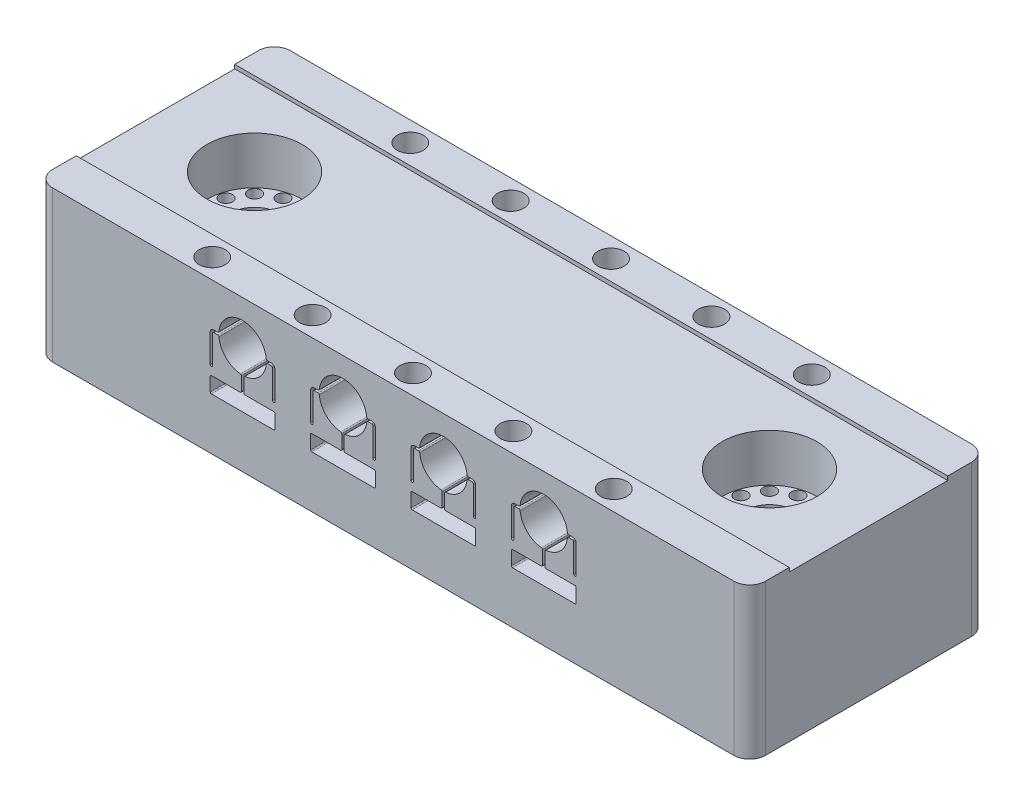
SolidWorks part; units mm, degrees
ref_plane "Front Plane" through (0, 0, 0) normal (0, 0, 1) x (1, 0, 0)
ref_plane "Top Plane" through (0, 0, 0) normal (0, 1, 0) x (1, 0, 0)
ref_plane "Right Plane" through (0, 0, 0) normal (1, 0, 0) x (0, 0, -1)
sketch "Sketch1" plane through (0, 0, 0) normal (0, 1, 0) x (1, 0, 0)
  line L0 (-45, 13) -> (-45, -13)
  line L3 (-43, -15) -> (43, -15)
  line L4 (45, -13) -> (45, 13)
  line L5 (43, 15) -> (-43, 15)
  line L6 (-32.5, 0) -> (32.5, 0) construction
  line L8 (-33.8159, 4.9109) -> (-36.095, 3.595) construction
  line L9 (-36.095, 3.595) -> (-37.4109, 1.3159) construction
  line L10 (-37.4109, 1.3159) -> (-37.4109, -1.3159) construction
  line L11 (-37.4109, -1.3159) -> (-36.095, -3.595) construction
  line L12 (-36.095, -3.595) -> (-33.8159, -4.9109) construction
  line L13 (-33.8159, -4.9109) -> (-31.1841, -4.9109) construction
  line L14 (-31.1841, -4.9109) -> (-28.905, -3.595) construction
  line L15 (-28.905, -3.595) -> (-27.5891, -1.3159) construction
  line L16 (-27.5891, -1.3159) -> (-27.5891, 1.3159) construction
  line L17 (-27.5891, 1.3159) -> (-28.905, 3.595) construction
  line L18 (-28.905, 3.595) -> (-31.1841, 4.9109) construction
  line L19 (-31.1841, 4.9109) -> (-33.8159, 4.9109) construction
  line L20 (33.8159, 4.9109) -> (31.1841, 4.9109) construction
  line L21 (31.1841, 4.9109) -> (28.905, 3.595) construction
  line L22 (28.905, 3.595) -> (27.5891, 1.3159) construction
  line L23 (27.5891, 1.3159) -> (27.5891, -1.3159) construction
  line L24 (27.5891, -1.3159) -> (28.905, -3.595) construction
  line L25 (28.905, -3.595) -> (31.1841, -4.9109) construction
  line L26 (31.1841, -4.9109) -> (33.8159, -4.9109) construction
  line L27 (33.8159, -4.9109) -> (36.095, -3.595) construction
  line L28 (36.095, -3.595) -> (37.4109, -1.3159) construction
  line L29 (37.4109, -1.3159) -> (37.4109, 1.3159) construction
  line L30 (37.4109, 1.3159) -> (36.095, 3.595) construction
  line L31 (36.095, 3.595) -> (33.8159, 4.9109) construction
  circle A2 centre (-32.5, 0) radius 3
  circle A3 centre (32.5, 0) radius 3
  circle A17 centre (32.5, 0) radius 6 construction
  circle A18 centre (-32.5, 0) radius 6 construction
  circle A19 centre (-31.1841, 4.9109) radius 0.9159 construction
  circle A20 centre (-31.1841, 4.9109) radius 0.8159
  circle A21 centre (-32.5, 0) radius 4.9109 construction
  circle A22 centre (-33.8159, 4.9109) radius 0.8159
  circle A23 centre (-33.8159, 4.9109) radius 1.8159 construction
  circle A24 centre (-36.095, 3.595) radius 0.8159
  circle A25 centre (-37.4109, 1.3159) radius 0.8159
  circle A26 centre (-37.4109, -1.3159) radius 0.8159
  circle A27 centre (-36.095, -3.595) radius 0.8159
  circle A28 centre (-33.8159, -4.9109) radius 0.8159
  circle A29 centre (-31.1841, -4.9109) radius 0.8159
  circle A30 centre (-28.905, -3.595) radius 0.8159
  circle A31 centre (-27.5891, -1.3159) radius 0.8159
  circle A32 centre (-27.5891, 1.3159) radius 0.8159
  circle A33 centre (-28.905, 3.595) radius 0.8159
  circle A34 centre (32.5, 0) radius 4.9109 construction
  circle A35 centre (31.1841, 4.9109) radius 0.8159
  circle A36 centre (33.8159, 4.9109) radius 0.8159
  circle A37 centre (36.095, 3.595) radius 0.8159
  circle A38 centre (37.4109, 1.3159) radius 0.8159
  circle A39 centre (37.4109, -1.3159) radius 0.8159
  circle A40 centre (36.095, -3.595) radius 0.8159
  circle A41 centre (33.8159, -4.9109) radius 0.8159
  circle A42 centre (31.1841, -4.9109) radius 0.8159
  circle A43 centre (28.905, -3.595) radius 0.8159
  circle A44 centre (27.5891, -1.3159) radius 0.8159
  circle A45 centre (27.5891, 1.3159) radius 0.8159
  circle A46 centre (28.905, 3.595) radius 0.8159
  arc A47 (43, -15) -> (45, -13) centre (43, -13) ccw
  arc A48 (-45, -13) -> (-43, -15) centre (-43, -13) ccw
  arc A49 (-45, 13) -> (-43, 15) centre (-43, 13) cw
  arc A50 (45, 13) -> (43, 15) centre (43, 13) ccw
  point P2 (-45, 0)
  point P6 (0, 15)
  point P72 (-45, 15)
  point P75 (45, 15)
  dimension "D1" = 90
  dimension "D2" = 12
  dimension "D3" = 65
  dimension "D4" = 6
  dimension "D5" = 30
  dimension "D6" = 0.1
  dimension "D7" = 1.6317
  dimension "D8" = 1
  dimension "D9" = 2
extrude "Boss-Extrude1" add sketch "Sketch1" along normal blind 19.05
sketch "Sketch2" plane through (0, 19.05, 0) normal (0, 1, 0) x (1, 0, 0)
  circle A0 centre (32.5, 0) radius 6 construction
  circle A1 centre (-32.5, 0) radius 6 construction
  circle A2 centre (32.5, 0) radius 6
  circle A3 centre (-32.5, 0) radius 6
extrude "Cut-Extrude1" cut sketch "Sketch2" against normal blind 6.5
sketch "Sketch3" plane through (0, 0, 15) normal (0, 0, 1) x (1, 0, 0)
  line L0 (0, 19.05) -> (0, 13.55) construction
  line L1 (-43, 19.05) -> (43, 19.05) construction
  line L2 (-22.1427, 13.7) -> (-22.6427, 13.7)
  line L3 (-22.1427, 13.4) -> (-22.6427, 13.4)
  line L4 (-23.0927, 13.25) -> (-23.0927, 9.7)
  line L5 (-22.7927, 13.25) -> (-22.7927, 9.7)
  line L6 (-15.8714, 13.7) -> (-15.3714, 13.7)
  line L7 (-15.8714, 13.4) -> (-15.3714, 13.4)
  line L8 (-15.2214, 13.25) -> (-15.2214, 9.7)
  line L9 (-14.9214, 13.25) -> (-14.9214, 9.7)
  line L10 (-19.157, 10.4143) -> (-19.157, 8.7)
  line L11 (-19.307, 8.55) -> (-22.9427, 8.55)
  line L12 (-18.857, 10.4143) -> (-18.857, 8.7)
  line L13 (-18.707, 8.55) -> (-15.0714, 8.55)
  line L14 (-22.9427, 6.5478) -> (-15.0714, 6.5478)
  line L15 (-23.0927, 8.4) -> (-23.0927, 6.6978)
  line L16 (-14.9214, 8.4) -> (-14.9214, 6.6978)
  line L17 (-19.007, 16.55) -> (-19.007, 19.05) construction
  line L18 (-22.1427, 13.4) -> (-22.1427, 13.7) construction
  line L19 (-22.9427, 9.55) -> (-22.9427, 8.55) construction
  line L20 (-19.157, 10.4143) -> (-18.857, 10.4143) construction
  line L21 (-21.507, 6.5478) -> (-21.507, 0) construction
  line L22 (-43, 0) -> (43, 0) construction
  line L23 (-16.507, 6.5478) -> (-16.507, 0) construction
  line L24 (-21.507, 3.2739) -> (-16.507, 3.2739) construction
  line L25 (-19.007, 3.2739) -> (-19.007, 6.5478) construction
  line L26 (-19.007, 8.55) -> (-19.007, 10.55) construction
  line L27 (-21.507, 6.5478) -> (-19.007, 8.05) construction
  line L28 (-19.007, 8.05) -> (-16.507, 6.5478) construction
  line L29 (-19.007, 13.55) -> (-14.9214, 13.55) construction
  line L30 (-14.9214, 13.55) -> (-10.4214, 13.55) construction
  line L31 (-10.4214, 13.55) -> (-6.3357, 13.55) construction
  line L32 (-6.3357, 13.55) -> (-2.25, 13.55) construction
  line L33 (-2.25, 13.55) -> (2.25, 13.55) construction
  line L34 (2.25, 13.55) -> (6.3357, 13.55) construction
  line L35 (6.3357, 13.55) -> (10.4214, 13.55) construction
  line L36 (10.4214, 13.55) -> (14.9214, 13.55) construction
  line L37 (14.9214, 13.55) -> (19.007, 13.55) construction
  arc A0 (-21.9934, 13.2643) -> (-19.2928, 10.5636) centre (-19.007, 13.55) ccw
  arc A1 (-22.6427, 13.7) -> (-23.0927, 13.25) centre (-22.6427, 13.25) ccw
  arc A2 (-22.6427, 13.4) -> (-22.7927, 13.25) centre (-22.6427, 13.25) ccw
  arc A3 (-23.0927, 9.7) -> (-22.7927, 9.7) centre (-22.9427, 9.7) ccw
  arc A4 (-15.3714, 13.7) -> (-14.9214, 13.25) centre (-15.3714, 13.25) cw
  arc A5 (-15.3714, 13.4) -> (-15.2214, 13.25) centre (-15.3714, 13.25) cw
  arc A6 (-15.2214, 9.7) -> (-14.9214, 9.7) centre (-15.0714, 9.7) ccw
  arc A7 (-16.0207, 13.8357) -> (-21.9934, 13.8357) centre (-19.007, 13.55) ccw
  arc A8 (-15.8714, 13.7) -> (-16.0207, 13.8357) centre (-15.8714, 13.85) cw
  arc A9 (-15.8714, 13.4) -> (-16.0207, 13.2643) centre (-15.8714, 13.25) ccw
  arc A10 (-22.1427, 13.4) -> (-21.9934, 13.2643) centre (-22.1427, 13.25) cw
  arc A11 (-22.1427, 13.7) -> (-21.9934, 13.8357) centre (-22.1427, 13.85) ccw
  arc A12 (-18.7213, 10.5636) -> (-16.0207, 13.2643) centre (-19.007, 13.55) ccw
  arc A13 (-19.157, 8.7) -> (-19.307, 8.55) centre (-19.307, 8.7) cw
  arc A14 (-22.9427, 8.55) -> (-23.0927, 8.4) centre (-22.9427, 8.4) ccw
  arc A15 (-23.0927, 6.6978) -> (-22.9427, 6.5478) centre (-22.9427, 6.6978) ccw
  arc A16 (-14.9214, 6.6978) -> (-15.0714, 6.5478) centre (-15.0714, 6.6978) cw
  arc A17 (-15.0714, 8.55) -> (-14.9214, 8.4) centre (-15.0714, 8.4) cw
  arc A18 (-18.857, 8.7) -> (-18.707, 8.55) centre (-18.707, 8.7) ccw
  arc A19 (-18.857, 10.4143) -> (-18.7213, 10.5636) centre (-18.707, 10.4143) cw
  arc A20 (-19.157, 10.4143) -> (-19.2928, 10.5636) centre (-19.307, 10.4143) ccw
  point P30 (-16.0108, 13.7)
  point P59 (-18.857, 10.5538)
  point P87 (-8.3785, 13.55)
  point P88 (0, 0)
  dimension "D1" = 2.5
  dimension "D2" = 1
  dimension "D5" = 3
  dimension "D3" = 0.3
  dimension "D4" = 5
  dimension "D6" = 2
  dimension "D7" = 118
  dimension "D8" = 0.5
  dimension "D9" = 0.5
  dimension "D10" = 4.5
extrude "Cut-Extrude2" cut sketch "Sketch3" against normal through all
pattern_linear "LPattern1" count 4 spacing 12.6714 along (1, 0, 0) of "Cut-Extrude2"
sketch "Sketch4" plane through (0, 19.05, 0) normal (0, 1, 0) x (1, 0, 0)
  line L0 (-45, -10) -> (45, -10)
  line L1 (-45, 13) -> (-45, -13) construction
  line L2 (45, -13) -> (45, 13) construction
  line L3 (45, -10) -> (45, 10)
  line L4 (45, 10) -> (-45, 10)
  line L5 (-45, 10) -> (-45, -10)
  line L6 (10.4214, -15) -> (14.9214, -15) construction
  line L7 (-2.25, -15) -> (2.25, -15) construction
  line L8 (-14.9214, -15) -> (-10.4214, -15) construction
  line L9 (10.4214, -15) -> (14.9214, -15) construction
  line L10 (-2.25, -15) -> (2.25, -15) construction
  line L11 (-14.9214, -15) -> (-10.4214, -15) construction
  line L12 (-14.9214, -15) -> (-23.0927, -15) construction
  line L13 (-43, -15) -> (43, -15) construction
  line L14 (-23.0927, -15) -> (-27.5927, -15) construction
  line L15 (-10.4214, -15) -> (-2.25, -15) construction
  line L16 (-25.3427, -15) -> (-25.3427, -10) construction
  line L17 (-25.3427, 10) -> (-25.3427, 15) construction
  line L18 (43, 15) -> (-43, 15) construction
  line L20 (14.9214, -15) -> (23.0927, -15) construction
  line L21 (23.0927, -15) -> (27.5927, -15) construction
  line L22 (25.3427, -15) -> (25.3427, -10) construction
  circle A0 centre (-25.3427, -12.5) radius 2.5 construction
  circle A1 centre (-25.3427, -12.5) radius 2 construction
  circle A2 centre (-25.3427, 12.5) radius 2.5 construction
  circle A3 centre (-25.3427, 12.5) radius 2 construction
  point P9 (-45, 0)
  point P21 (25.3427, -12.5)
  dimension "D1" = 0.5
  dimension "D2" = 4
sketch "Sketch5" plane through (0, 19.05, 0) normal (0, 1, 0) x (1, 0, 0)
  point P0 (-25.3427, -12.5)
  point P3 (-25.3427, 12.5)
hole_wizard "M4x0.7 Tapped Hole1" positions "Sketch5" profile "Sketch6" tap size "M4x0.7" standard "ANSI Metric"
sketch "Sketch6" plane through (-25.3427, 19.05, 12.5) normal (1, 0, 0) x (0, 0, 1)
  line L0 (0, 0) -> (0, 11.0914)
  line L1 (0, 11.0914) -> (1.65, 10.1)
  line L2 (1.65, 10.1) -> (1.65, 0)
  line L5 (1.65, 0) -> (0, 0)
  line L10 (0, 11.0914) -> (-1.65, 10.1) construction
  line L11 (0, -6.35) -> (0, 107.95) construction
  dimension "Tap Drill Dia." = 3.3
  dimension "Tap Drill Depth" = 10.1
  dimension "Drill Angle" = 118
cosmetic thread "Hole Thread1" parameters "D1"=8, "D2"=4
cosmetic thread "Hole Thread2" parameters "D1"=8, "D2"=4
pattern_linear "LPattern2" count 5 spacing 12.6714 along (1, 0, 0) of "M4x0.7 Tapped Hole1"
cosmetic thread "Hole Thread3" parameters "D1"=8, "D2"=4
cosmetic thread "Hole Thread4" parameters "D1"=8, "D2"=4
cosmetic thread "Hole Thread5" parameters "D1"=8, "D2"=4
cosmetic thread "Hole Thread6" parameters "D1"=8, "D2"=4
cosmetic thread "Hole Thread7" parameters "D1"=8, "D2"=4
cosmetic thread "Hole Thread8" parameters "D1"=8, "D2"=4
cosmetic thread "Hole Thread9" parameters "D1"=8, "D2"=4
cosmetic thread "Hole Thread10" parameters "D1"=8, "D2"=4
extrude "Cut-Extrude3" cut sketch "Sketch4" against normal blind 0.5
sketch "Sketch7" plane through (0, 0, 0) normal (0, -1, 0) x (1, 0, 0)
  line L0 (-22.9427, 15) -> (-15.0714, 15) construction
  line L1 (-22.9427, 15) -> (-15.0714, 15) construction
  line L2 (15.0714, 15) -> (22.9427, 15) construction
  line L3 (15.0714, 15) -> (22.9427, 15) construction
  line L4 (-19.007, 5) -> (-19.007, -5) construction
  circle A0 centre (-19.007, 5) radius 2.5
  circle A1 centre (-19.007, -5) radius 2.5
  point P6 (-19.007, 15)
  point P7 (19.007, 15)
  point P8 (-19.007, 0)
  dimension "D2" = 5
  dimension "D1" = 10
extrude "Cut-Extrude4" cut sketch "Sketch7" against normal up to surface (6.5478 mm away) up to face at (-19.007, 6.5478, 0)
pattern_linear "LPattern3" count 4 spacing 12.6714 along (1, 0, 0) of "Cut-Extrude4"
